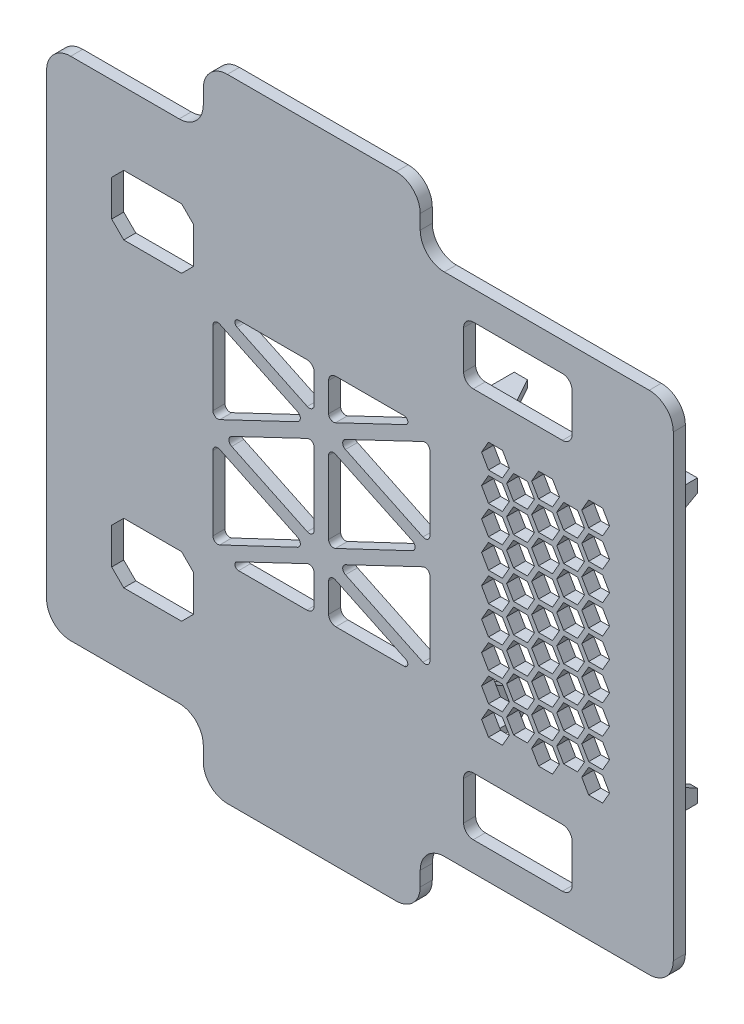
SolidWorks part; units mm, degrees
ref_plane "前视基准面" through (0, 0, 0) normal (0, 0, 1) x (1, 0, 0)
ref_plane "上视基准面" through (0, 0, 0) normal (0, 1, 0) x (1, 0, 0)
ref_plane "右视基准面" through (0, 0, 0) normal (1, 0, 0) x (0, 0, -1)
sketch "草图1" plane through (0, 0, 0) normal (0, 0, 1) x (1, 0, 0)
  line L2 (-130, 95) -> (-130, -95)
  line L3 (-120, -105) -> (-75, -105)
  line L4 (130, 95) -> (130, -95)
  line L5 (126.7518, 102.3765) -> (130, 105) construction
  line L6 (-130, -105) -> (-126.7518, -102.3765) construction
  line L9 (-65, -115) -> (-65, -121)
  line L10 (-55, -131) -> (15, -131)
  line L11 (25, -121) -> (25, -115)
  line L13 (35, -105) -> (120, -105)
  line L14 (126.7518, -102.3765) -> (130, -105) construction
  line L15 (-130, 105) -> (-126.7518, 102.3765) construction
  line L16 (-130, 0) -> (130, 0) construction
  line L17 (35, 105) -> (120, 105)
  line L18 (25, 121) -> (25, 115)
  line L19 (-55, 131) -> (15, 131)
  line L20 (-65, 115) -> (-65, 121)
  line L21 (-120, 105) -> (-75, 105)
  arc A1 (-120, -105) -> (-130, -95) centre (-120, -95) cw
  arc A3 (120, -105) -> (130, -95) centre (120, -95) ccw
  arc A8 (-65, -115) -> (-75, -105) centre (-75, -115) ccw
  arc A9 (25, -115) -> (35, -105) centre (35, -115) cw
  arc A10 (-55, -131) -> (-65, -121) centre (-55, -121) cw
  arc A11 (15, -131) -> (25, -121) centre (15, -121) ccw
  arc A12 (15, 131) -> (25, 121) centre (15, 121) cw
  arc A13 (-55, 131) -> (-65, 121) centre (-55, 121) ccw
  arc A14 (25, 115) -> (35, 105) centre (35, 115) ccw
  arc A15 (-65, 115) -> (-75, 105) centre (-75, 115) cw
  arc A16 (120, 105) -> (130, 95) centre (120, 95) cw
  arc A17 (-120, 105) -> (-130, 95) centre (-120, 95) ccw
  point P0 (0, 0)
  point P40 (25, -105)
  point P45 (25, 105)
  dimension "D2" = 10
  dimension "D3" = 65
  dimension "D4" = 10
  dimension "D5" = 105
  dimension "D7" = 10
  dimension "D8" = 10
  dimension "D10" = 10
  dimension "D12" = 10
  dimension "D13" = 105
  dimension "D18" = 90
  dimension "D19" = 6
extrude "凸台-拉伸1" add sketch "草图1" along normal blind 5
sketch "草图4" plane through (0, 0, 0) normal (0, 0, -1) x (-1, 0, 0)
  line L0 (-39, -47.5) -> (-39, -58.5)
  line L1 (-39, -58.5) -> (-50, -58.5)
  line L2 (-50, -58.5) -> (-50, -55.5)
  line L3 (-50, -55.5) -> (-42, -55.5)
  line L4 (-42, -55.5) -> (-42, -47.5)
  line L5 (-42, -47.5) -> (-39, -47.5)
  line L6 (-130, 0) -> (-25.5592, 0) construction
  line L7 (-130, -95) -> (-130, 95) construction
  line L10 (-130, -95) -> (-130, 95) construction
  dimension "D1" = 11
  dimension "D2" = 11
  dimension "D3" = 3
  dimension "D4" = 3
  dimension "D5" = 80
  dimension "D7" = 55.5
extrude "凸台-拉伸2" add sketch "草图4" along normal blind 20
sketch "草图5" plane through (0, -58.5, 0) normal (0, -1, 0) x (1, 0, 0)
  line L0 (50, -10) -> (44.5, -20)
  line L1 (50, -20) -> (50, 0) construction
  line L2 (50, -20) -> (39, -20) construction
  line L3 (44.5, -20) -> (50, -20)
  line L4 (50, -20) -> (50, -10)
  dimension "D1" = 10
  dimension "D2" = 5.5
extrude "切除-拉伸3" cut sketch "草图5" against normal blind 10
sketch "草图6" plane through (39, 0, 0) normal (-1, 0, 0) x (0, 0, 1)
  line L0 (-20, -53) -> (-10, -47.5)
  line L1 (-20, -58.5) -> (-20, -47.5) construction
  line L2 (-20, -47.5) -> (0, -47.5) construction
  line L3 (-10, -47.5) -> (-20, -47.5)
  line L4 (-20, -47.5) -> (-20, -53)
  dimension "D1" = 10
  dimension "D2" = 5.5
extrude "切除-拉伸4" cut sketch "草图6" against normal blind 10
ref_plane "基准面2" through (77, 0, 0) normal (1, 0, 0) x (0, 0, -1)
mirror "镜向1" about plane through (77, 0, 0) normal (1, 0, 0) of "凸台-拉伸2", "切除-拉伸4", "切除-拉伸3"
mirror "镜向2" about plane through (0, 0, 0) normal (0, 1, 0) of "镜向1"
sketch "草图7" plane through (0, 0, 0) normal (0, 0, -1) x (-1, 0, 0)
  line L4 (-112, -55.5) -> (-104, -55.5) construction
  line L5 (-112, 47.5) -> (-112, 55.5) construction
  line L6 (-112, 55.5) -> (-104, 55.5) construction
  line L7 (-92.013, 36) -> (-94.8997, 41)
  line L8 (-94.8997, 41) -> (-100.6732, 41)
  line L9 (-100.6732, 41) -> (-103.56, 36)
  line L10 (-103.56, 36) -> (-100.6732, 31)
  line L11 (-100.6732, 31) -> (-94.8997, 31)
  line L12 (-94.8997, 31) -> (-92.013, 36)
  line L13 (-77.0019, 36) -> (-97.7865, 36) construction
  line L14 (-74.1151, 31) -> (-71.2284, 36)
  line L15 (-71.2284, 36) -> (-74.1151, 41)
  line L16 (-74.1151, 41) -> (-79.8886, 41)
  line L17 (-79.8886, 41) -> (-82.7754, 36)
  line L18 (-82.7754, 36) -> (-79.8886, 31)
  line L19 (-79.8886, 31) -> (-74.1151, 31)
  line L20 (-92.013, 24) -> (-94.8997, 29)
  line L21 (-93.1677, 30) -> (-90.2809, 25)
  line L22 (-90.2809, 25) -> (-84.5074, 25)
  line L23 (-84.5074, 25) -> (-81.6207, 30)
  line L24 (-81.6207, 30) -> (-84.5074, 35)
  line L25 (-84.5074, 35) -> (-90.2809, 35)
  line L26 (-90.2809, 35) -> (-93.1677, 30)
  line L27 (-84.5074, 37) -> (-81.6207, 42)
  line L28 (-81.6207, 42) -> (-84.5074, 47)
  line L29 (-84.5074, 47) -> (-90.2809, 47)
  line L30 (-90.2809, 47) -> (-93.1677, 42)
  line L31 (-93.1677, 42) -> (-90.2809, 37)
  line L32 (-90.2809, 37) -> (-84.5074, 37)
  line L33 (-79.8886, 43) -> (-74.1151, 43)
  line L34 (-74.1151, 43) -> (-71.2284, 48)
  line L35 (-71.2284, 48) -> (-74.1151, 53)
  line L36 (-74.1151, 53) -> (-79.8886, 53)
  line L37 (-79.8886, 53) -> (-82.7754, 48)
  line L38 (-82.7754, 48) -> (-79.8886, 43)
  line L39 (-94.8997, 43) -> (-92.013, 48)
  line L40 (-92.013, 48) -> (-94.8997, 53)
  line L41 (-94.8997, 53) -> (-100.6732, 53)
  line L42 (-100.6732, 53) -> (-103.56, 48)
  line L43 (-103.56, 48) -> (-100.6732, 43)
  line L44 (-100.6732, 43) -> (-94.8997, 43)
  line L45 (-72.3831, 42) -> (-69.4963, 37)
  line L46 (-69.4963, 37) -> (-63.7228, 37)
  line L47 (-63.7228, 37) -> (-60.8361, 42)
  line L48 (-60.8361, 42) -> (-63.7228, 47)
  line L49 (-63.7228, 47) -> (-69.4963, 47)
  line L50 (-69.4963, 47) -> (-72.3831, 42)
  line L51 (-94.8997, 29) -> (-100.6732, 29)
  line L52 (-100.6732, 29) -> (-103.56, 24)
  line L53 (-103.56, 24) -> (-100.6732, 19)
  line L54 (-100.6732, 19) -> (-94.8997, 19)
  line L55 (-94.8997, 19) -> (-92.013, 24)
  line L56 (-93.1677, 18) -> (-90.2809, 13)
  line L57 (-90.2809, 13) -> (-84.5074, 13)
  line L58 (-84.5074, 13) -> (-81.6207, 18)
  line L59 (-81.6207, 18) -> (-84.5074, 23)
  line L60 (-84.5074, 23) -> (-90.2809, 23)
  line L61 (-90.2809, 23) -> (-93.1677, 18)
  line L62 (-74.1151, 19) -> (-71.2284, 24)
  line L63 (-71.2284, 24) -> (-74.1151, 29)
  line L64 (-74.1151, 29) -> (-79.8886, 29)
  line L65 (-79.8886, 29) -> (-82.7754, 24)
  line L66 (-82.7754, 24) -> (-79.8886, 19)
  line L67 (-79.8886, 19) -> (-74.1151, 19)
  line L68 (-72.3831, 30) -> (-69.4963, 25)
  line L69 (-69.4963, 25) -> (-63.7228, 25)
  line L70 (-63.7228, 25) -> (-60.8361, 30)
  line L71 (-60.8361, 30) -> (-63.7228, 35)
  line L72 (-63.7228, 35) -> (-69.4963, 35)
  line L73 (-69.4963, 35) -> (-72.3831, 30)
  line L74 (-92.013, 12) -> (-94.8997, 17)
  line L75 (-94.8997, 17) -> (-100.6732, 17)
  line L76 (-100.6732, 17) -> (-103.56, 12)
  line L77 (-103.56, 12) -> (-100.6732, 7)
  line L78 (-100.6732, 7) -> (-94.8997, 7)
  line L79 (-94.8997, 7) -> (-92.013, 12)
  line L80 (-93.1677, 6) -> (-90.2809, 1)
  line L81 (-90.2809, 1) -> (-84.5074, 1)
  line L82 (-84.5074, 1) -> (-81.6207, 6)
  line L83 (-81.6207, 6) -> (-84.5074, 11)
  line L84 (-84.5074, 11) -> (-90.2809, 11)
  line L85 (-90.2809, 11) -> (-93.1677, 6)
  line L86 (-74.1151, 7) -> (-71.2284, 12)
  line L87 (-71.2284, 12) -> (-74.1151, 17)
  line L88 (-74.1151, 17) -> (-79.8886, 17)
  line L89 (-79.8886, 17) -> (-82.7754, 12)
  line L90 (-82.7754, 12) -> (-79.8886, 7)
  line L91 (-79.8886, 7) -> (-74.1151, 7)
  line L92 (-72.3831, 18) -> (-69.4963, 13)
  line L93 (-69.4963, 13) -> (-63.7228, 13)
  line L94 (-63.7228, 13) -> (-60.8361, 18)
  line L95 (-60.8361, 18) -> (-63.7228, 23)
  line L96 (-63.7228, 23) -> (-69.4963, 23)
  line L97 (-69.4963, 23) -> (-72.3831, 18)
  line L98 (-92.013, 0) -> (-94.8997, 5)
  line L99 (-94.8997, 5) -> (-100.6732, 5)
  line L100 (-100.6732, 5) -> (-103.56, 0)
  line L101 (-103.56, 0) -> (-100.6732, -5)
  line L102 (-100.6732, -5) -> (-94.8997, -5)
  line L103 (-94.8997, -5) -> (-92.013, 0)
  line L104 (-93.1677, -6) -> (-90.2809, -11)
  line L105 (-90.2809, -11) -> (-84.5074, -11)
  line L106 (-84.5074, -11) -> (-81.6207, -6)
  line L107 (-81.6207, -6) -> (-84.5074, -1)
  line L108 (-84.5074, -1) -> (-90.2809, -1)
  line L109 (-90.2809, -1) -> (-93.1677, -6)
  line L110 (-74.1151, -5) -> (-71.2284, 0)
  line L111 (-71.2284, 0) -> (-74.1151, 5)
  line L112 (-74.1151, 5) -> (-79.8886, 5)
  line L113 (-79.8886, 5) -> (-82.7754, 0)
  line L114 (-82.7754, 0) -> (-79.8886, -5)
  line L115 (-79.8886, -5) -> (-74.1151, -5)
  line L116 (-72.3831, 6) -> (-69.4963, 1)
  line L117 (-69.4963, 1) -> (-63.7228, 1)
  line L118 (-63.7228, 1) -> (-60.8361, 6)
  line L119 (-60.8361, 6) -> (-63.7228, 11)
  line L120 (-63.7228, 11) -> (-69.4963, 11)
  line L121 (-69.4963, 11) -> (-72.3831, 6)
  line L122 (-92.013, -12) -> (-94.8997, -7)
  line L123 (-94.8997, -7) -> (-100.6732, -7)
  line L124 (-100.6732, -7) -> (-103.56, -12)
  line L125 (-103.56, -12) -> (-100.6732, -17)
  line L126 (-100.6732, -17) -> (-94.8997, -17)
  line L127 (-94.8997, -17) -> (-92.013, -12)
  line L128 (-93.1677, -18) -> (-90.2809, -23)
  line L129 (-90.2809, -23) -> (-84.5074, -23)
  line L130 (-84.5074, -23) -> (-81.6207, -18)
  line L131 (-81.6207, -18) -> (-84.5074, -13)
  line L132 (-84.5074, -13) -> (-90.2809, -13)
  line L133 (-90.2809, -13) -> (-93.1677, -18)
  line L134 (-74.1151, -17) -> (-71.2284, -12)
  line L135 (-71.2284, -12) -> (-74.1151, -7)
  line L136 (-74.1151, -7) -> (-79.8886, -7)
  line L137 (-79.8886, -7) -> (-82.7754, -12)
  line L138 (-82.7754, -12) -> (-79.8886, -17)
  line L139 (-79.8886, -17) -> (-74.1151, -17)
  line L140 (-72.3831, -6) -> (-69.4963, -11)
  line L141 (-69.4963, -11) -> (-63.7228, -11)
  line L142 (-63.7228, -11) -> (-60.8361, -6)
  line L143 (-60.8361, -6) -> (-63.7228, -1)
  line L144 (-63.7228, -1) -> (-69.4963, -1)
  line L145 (-69.4963, -1) -> (-72.3831, -6)
  line L146 (-92.013, -24) -> (-94.8997, -19)
  line L147 (-94.8997, -19) -> (-100.6732, -19)
  line L148 (-100.6732, -19) -> (-103.56, -24)
  line L149 (-103.56, -24) -> (-100.6732, -29)
  line L150 (-100.6732, -29) -> (-94.8997, -29)
  line L151 (-94.8997, -29) -> (-92.013, -24)
  line L152 (-93.1677, -30) -> (-90.2809, -35)
  line L153 (-90.2809, -35) -> (-84.5074, -35)
  line L154 (-84.5074, -35) -> (-81.6207, -30)
  line L155 (-81.6207, -30) -> (-84.5074, -25)
  line L156 (-84.5074, -25) -> (-90.2809, -25)
  line L157 (-90.2809, -25) -> (-93.1677, -30)
  line L158 (-74.1151, -29) -> (-71.2284, -24)
  line L159 (-71.2284, -24) -> (-74.1151, -19)
  line L160 (-74.1151, -19) -> (-79.8886, -19)
  line L161 (-79.8886, -19) -> (-82.7754, -24)
  line L162 (-82.7754, -24) -> (-79.8886, -29)
  line L163 (-79.8886, -29) -> (-74.1151, -29)
  line L164 (-72.3831, -18) -> (-69.4963, -23)
  line L165 (-69.4963, -23) -> (-63.7228, -23)
  line L166 (-63.7228, -23) -> (-60.8361, -18)
  line L167 (-60.8361, -18) -> (-63.7228, -13)
  line L168 (-63.7228, -13) -> (-69.4963, -13)
  line L169 (-69.4963, -13) -> (-72.3831, -18)
  line L170 (-92.013, -36) -> (-94.8997, -31)
  line L171 (-94.8997, -31) -> (-100.6732, -31)
  line L172 (-100.6732, -31) -> (-103.56, -36)
  line L173 (-103.56, -36) -> (-100.6732, -41)
  line L174 (-100.6732, -41) -> (-94.8997, -41)
  line L175 (-94.8997, -41) -> (-92.013, -36)
  line L176 (-93.1677, -42) -> (-90.2809, -47)
  line L177 (-90.2809, -47) -> (-84.5074, -47)
  line L178 (-84.5074, -47) -> (-81.6207, -42)
  line L179 (-81.6207, -42) -> (-84.5074, -37)
  line L180 (-84.5074, -37) -> (-90.2809, -37)
  line L181 (-90.2809, -37) -> (-93.1677, -42)
  line L182 (-74.1151, -41) -> (-71.2284, -36)
  line L183 (-71.2284, -36) -> (-74.1151, -31)
  line L184 (-74.1151, -31) -> (-79.8886, -31)
  line L185 (-79.8886, -31) -> (-82.7754, -36)
  line L186 (-82.7754, -36) -> (-79.8886, -41)
  line L187 (-79.8886, -41) -> (-74.1151, -41)
  line L188 (-72.3831, -30) -> (-69.4963, -35)
  line L189 (-69.4963, -35) -> (-63.7228, -35)
  line L190 (-63.7228, -35) -> (-60.8361, -30)
  line L191 (-60.8361, -30) -> (-63.7228, -25)
  line L192 (-63.7228, -25) -> (-69.4963, -25)
  line L193 (-69.4963, -25) -> (-72.3831, -30)
  line L194 (-92.013, -48) -> (-94.8997, -43)
  line L195 (-94.8997, -43) -> (-100.6732, -43)
  line L196 (-100.6732, -43) -> (-103.56, -48)
  line L197 (-103.56, -48) -> (-100.6732, -53)
  line L198 (-100.6732, -53) -> (-94.8997, -53)
  line L199 (-94.8997, -53) -> (-92.013, -48)
  line L206 (-74.1151, -53) -> (-71.2284, -48)
  line L207 (-71.2284, -48) -> (-74.1151, -43)
  line L208 (-74.1151, -43) -> (-79.8886, -43)
  line L209 (-79.8886, -43) -> (-82.7754, -48)
  line L210 (-82.7754, -48) -> (-79.8886, -53)
  line L211 (-79.8886, -53) -> (-74.1151, -53)
  line L212 (-72.3831, -42) -> (-69.4963, -47)
  line L213 (-69.4963, -47) -> (-63.7228, -47)
  line L214 (-63.7228, -47) -> (-60.8361, -42)
  line L215 (-60.8361, -42) -> (-63.7228, -37)
  line L216 (-63.7228, -37) -> (-69.4963, -37)
  line L217 (-69.4963, -37) -> (-72.3831, -42)
  line L218 (-61.9908, 36) -> (-59.104, 31)
  line L219 (-61.9908, 48) -> (-59.104, 43)
  line L220 (-59.104, 43) -> (-53.3305, 43)
  line L221 (-53.3305, 43) -> (-50.4438, 48)
  line L222 (-50.4438, 48) -> (-53.3305, 53)
  line L223 (-53.3305, 53) -> (-59.104, 53)
  line L224 (-59.104, 53) -> (-61.9908, 48)
  line L225 (-59.104, 31) -> (-53.3305, 31)
  line L226 (-53.3305, 31) -> (-50.4438, 36)
  line L227 (-50.4438, 36) -> (-53.3305, 41)
  line L228 (-53.3305, 41) -> (-59.104, 41)
  line L229 (-59.104, 41) -> (-61.9908, 36)
  line L230 (-61.9908, 24) -> (-59.104, 19)
  line L231 (-59.104, 19) -> (-53.3305, 19)
  line L232 (-53.3305, 19) -> (-50.4438, 24)
  line L233 (-50.4438, 24) -> (-53.3305, 29)
  line L234 (-53.3305, 29) -> (-59.104, 29)
  line L235 (-59.104, 29) -> (-61.9908, 24)
  line L236 (-61.9908, 12) -> (-59.104, 7)
  line L237 (-59.104, 7) -> (-53.3305, 7)
  line L238 (-53.3305, 7) -> (-50.4438, 12)
  line L239 (-50.4438, 12) -> (-53.3305, 17)
  line L240 (-53.3305, 17) -> (-59.104, 17)
  line L241 (-59.104, 17) -> (-61.9908, 12)
  line L242 (-61.9908, 0) -> (-59.104, -5)
  line L243 (-59.104, -5) -> (-53.3305, -5)
  line L244 (-53.3305, -5) -> (-50.4438, 0)
  line L245 (-50.4438, 0) -> (-53.3305, 5)
  line L246 (-53.3305, 5) -> (-59.104, 5)
  line L247 (-59.104, 5) -> (-61.9908, 0)
  line L248 (-61.9908, -12) -> (-59.104, -17)
  line L249 (-59.104, -17) -> (-53.3305, -17)
  line L250 (-53.3305, -17) -> (-50.4438, -12)
  line L251 (-50.4438, -12) -> (-53.3305, -7)
  line L252 (-53.3305, -7) -> (-59.104, -7)
  line L253 (-59.104, -7) -> (-61.9908, -12)
  line L254 (-61.9908, -24) -> (-59.104, -29)
  line L255 (-59.104, -29) -> (-53.3305, -29)
  line L256 (-53.3305, -29) -> (-50.4438, -24)
  line L257 (-50.4438, -24) -> (-53.3305, -19)
  line L258 (-53.3305, -19) -> (-59.104, -19)
  line L259 (-59.104, -19) -> (-61.9908, -24)
  line L260 (-61.9908, -36) -> (-59.104, -41)
  line L261 (-59.104, -41) -> (-53.3305, -41)
  line L262 (-53.3305, -41) -> (-50.4438, -36)
  line L263 (-50.4438, -36) -> (-53.3305, -31)
  line L264 (-53.3305, -31) -> (-59.104, -31)
  line L265 (-59.104, -31) -> (-61.9908, -36)
  line L266 (-61.9908, -48) -> (-59.104, -53)
  line L267 (-59.104, -53) -> (-53.3305, -53)
  line L268 (-53.3305, -53) -> (-50.4438, -48)
  line L269 (-50.4438, -48) -> (-53.3305, -43)
  line L270 (-53.3305, -43) -> (-59.104, -43)
  line L271 (-59.104, -43) -> (-61.9908, -48)
  line L272 (-93.1677, -54) -> (-90.2809, -59) [skipped]
  line L273 (-90.2809, -59) -> (-84.5074, -59) [skipped]
  line L274 (-84.5074, -59) -> (-81.6207, -54) [skipped]
  line L275 (-81.6207, -54) -> (-84.5074, -49) [skipped]
  line L276 (-84.5074, -49) -> (-90.2809, -49) [skipped]
  line L277 (-90.2809, -49) -> (-93.1677, -54) [skipped]
  circle A0 centre (-97.7865, 36) radius 5 construction
  circle A1 centre (-77.0019, 36) radius 5 construction
  circle A2 centre (-87.3942, 30) radius 5 construction
  circle A3 centre (-87.3942, 42) radius 5 construction
  circle A4 centre (-77.0019, 48) radius 5 construction
  circle A5 centre (-97.7865, 48) radius 5 construction
  circle A6 centre (-66.6096, 42) radius 5 construction
  circle A7 centre (-56.2173, 48) radius 5 construction
  point P4 (-87.3942, 37)
  dimension "D1" = 2
  dimension "D3" = 10
  dimension "D4" = 10
  dimension "D5" = 2
  dimension "D7" = 10
  dimension "D11" = 10
  dimension "D14" = 10
  dimension "D15" = 10
  dimension "D20" = 10
  dimension "D2" = 2
  dimension "D6" = 2
  dimension "D8" = 2
  dimension "D9" = 2
  dimension "D10" = 2
  dimension "D12" = 2
  dimension "D13" = 2
  dimension "D16" = 2
  dimension "D17" = 2
  dimension "D19" = 2
  dimension "D21" = 9
  dimension "D22" = 2.5
  dimension "D23" = 2.5
  dimension "D24" = 8.44
  dimension "D18" = 8
extrude "切除-拉伸5" cut sketch "草图7" against normal blind 5
sketch "草图8" plane through (0, 0, 0) normal (0, 0, -1) x (-1, 0, 0)
  line L0 (-75.3677, 120) -> (-75.3677, -120)
  line L1 (-100.0285, 77.2863) -> (-100.0285, -77.2863)
  line L2 (-100.0285, 77.2863) -> (-75.3677, 120)
  line L3 (-100.0285, -77.2863) -> (-75.3677, -120)
  line L4 (-37.1297, 0) -> (-146.8562, 0) construction
  dimension "D1" = 30
  dimension "D2" = 30
  dimension "D3" = 120
  dimension "D4" = 120
sketch "草图9" plane through (0, 0, 0) normal (0, 0, -1) x (-1, 0, 0)
  line L0 (148.8518, 0) -> (-37.1297, 0) construction
  line L1 (-29, 41) -> (-29, 4)
  line L2 (-25, -45) -> (13, -45)
  line L3 (61, -41) -> (61, -4)
  line L4 (57, 45) -> (19, 45)
  line L14 (-29, 41) -> (9.8049, 22.5)
  line L15 (57, 0) -> (19, -18.1163)
  line L16 (130, 95) -> (130, -95) construction
  line L17 (63, 93) -> (118, 93)
  line L18 (63, 93) -> (63, 66)
  line L19 (63, 66) -> (118, 66)
  line L20 (118, 93) -> (118, 66)
  line L21 (75, 105) -> (120, 105) construction
  line L22 (63, -66) -> (118, -66)
  line L23 (118, -93) -> (118, -66)
  line L24 (63, -93) -> (118, -93)
  line L25 (63, -93) -> (63, -66)
  line L26 (-120, 105) -> (-35, 105) construction
  line L27 (-43, 93) -> (-88, 93)
  line L28 (-43, 93) -> (-43, 69)
  line L29 (-43, 69) -> (-88, 69)
  line L30 (-88, 93) -> (-88, 69)
  line L31 (-130, -95) -> (-130, 95) construction
  line L32 (-43, -69) -> (-88, -69)
  line L33 (-88, -93) -> (-88, -69)
  line L34 (-43, -93) -> (-88, -93)
  line L35 (-43, -93) -> (-43, -69)
  line L36 (-25, 45) -> (13, 26.8837)
  line L37 (-25, -45) -> (13, -26.8837)
  line L38 (61, 41) -> (22.0746, 22.5575)
  line L39 (-25.5359, 0) -> (13, -18.258)
  line L40 (57, 45) -> (19, 26.8837)
  line L41 (57, -45) -> (19, -26.8837)
  line L42 (16, 61.4977) -> (16, -60.5731) construction
  line L43 (13, 45) -> (13, 26.8837)
  line L44 (19, 45) -> (19, 26.8837)
  line L45 (13, 18.258) -> (13, -18.258)
  line L46 (9.8049, 22.5) -> (-29, 4)
  line L47 (19, 18.1163) -> (57, 0)
  line L48 (22.0746, 22.5575) -> (61, 4)
  line L49 (13, 18.258) -> (-25.5359, 0)
  line L50 (19, 18.1163) -> (19, -18.1163)
  line L51 (22.0746, -22.5575) -> (61, -41)
  line L52 (9.8049, -22.5) -> (-29, -41)
  line L53 (9.8049, -22.5) -> (-29, -4)
  line L54 (22.0746, -22.5575) -> (61, -4)
  line L55 (13, -26.8837) -> (13, -45)
  line L56 (19, -26.8837) -> (19, -45)
  line L57 (13, 45) -> (-25, 45)
  line L58 (-29, -4) -> (-29, -41)
  line L59 (19, -45) -> (57, -45)
  line L60 (61, 4) -> (61, 41)
  line L61 (-44, 41) -> (-44, -37.8122) construction
  dimension "D1" = 45
  dimension "D2" = 45
  dimension "D3" = 15
  dimension "D4" = 90
  dimension "D5" = 1
  dimension "D7" = 12
  dimension "D8" = 12
  dimension "D9" = 27
  dimension "D10" = 55
  dimension "D11" = 12
  dimension "D12" = 45
  dimension "D13" = 42
  dimension "D14" = 24
  dimension "D21" = 4
  dimension "D22" = 4
  dimension "D23" = 4
  dimension "D24" = 4
  dimension "D26" = 4
  dimension "D27" = 3
  dimension "D28" = 45
extrude "切除-拉伸6" cut sketch "草图9" against normal blind 5 contours L27 L30 L29 L28 | L34 L35 L32 L33 | L4 L44 L40 | L48 L60 L38 | L47 L50 L15 | L54 L51 L3 | L56 L59 L41 | L55 L37 L2 | L53 L58 L52 | L45 L49 L39 | L46 L14 L1 | L43 L57 L36 | L57 L36 L43 region at (16.065, 22.5, 0) region at (-0.3333, -38.9612, 0) region at (-48.0249, -22.5192, 0) region at (-31.6667, 38.9612, 0) region at (-31.6667, 0, 0) region at (65.5, 81, 0) region at (65.5, -81, 0) region at (-0.3333, 38.9612, 0) region at (-48.0249, 22.5192, 0) region at (-0.1547, 0, 0) region at (-31.6667, -38.9612, 0) region at (16.065, -22.5, 0)
fillet "圆角1" radius 4 8 edges at (43, -93, 2.5) (88, -69, 2.5) (43, -69, 2.5) (88, -93, 2.5) (88, 69, 2.5) (43, 69, 2.5) (43, 93, 2.5) (88, 93, 2.5)
fillet "圆角2" radius 1.5 4 edges at (25, -45, 2.5) (-57, -45, 2.5) (25, 45, 2.5) (-57, 45, 2.5)
fillet "圆角3" radius 2 22 edges at (29, -4, 2.5) (29, 4, 2.5) (-13, -18.258, 2.5) (-61, -41, 2.5) (-61, 4, 2.5) (-13, -26.8837, 2.5) (-13, 18.258, 2.5) (-61, -4, 2.5) (-22.0746, -22.5575, 2.5) (25.5359, 0, 2.5) (-22.0746, 22.5575, 2.5) (-61, 41, 2.5) (-19, 26.8837, 2.5) (-19, -26.8837, 2.5) (-19, -18.1163, 2.5) (29, -41, 2.5) (29, 41, 2.5) (-57, 0, 2.5) (-9.8049, -22.5, 2.5) (-13, 26.8837, 2.5) (-9.8049, 22.5, 2.5) (-19, 18.1163, 2.5)
fillet "圆角4" radius 3 4 edges at (-13, -45, 2.5) (-13, 45, 2.5) (-19, -45, 2.5) (-19, 45, 2.5)
sketch "草图10" plane through (0, 0, 0) normal (0, 0, -1) x (-1, 0, 0)
  line L0 (-37.1297, 0) -> (-146.8562, 0) construction
  line L1 (-37.1297, 0) -> (-146.8562, 0) construction
  circle A0 centre (-119.4219, 72.4542) radius 1.8 construction
  circle A1 centre (-109.0164, 65.5279) radius 1.8 construction
  circle A2 centre (-104.184, 95.3465) radius 1.8 construction
  circle A3 centre (-93.7785, 88.4202) radius 1.8 construction
  circle A4 centre (-3.75, 104) radius 2.15 construction
  circle A5 centre (-3.75, 104) radius 2.15
  circle A6 centre (-3.75, -104) radius 2.15
  circle A11 centre (-13.0267, 121.679) radius 2.5 construction
  circle A12 centre (56.0941, 121.679) radius 2.45 construction
  circle A13 centre (30.0941, 121.679) radius 2.5 construction
  circle A14 centre (12.9733, 121.679) radius 2.45 construction
  circle A15 centre (-119.4219, 72.4542) radius 1.8
  circle A16 centre (-109.0164, 65.5279) radius 1.8
  circle A17 centre (-104.184, 95.3465) radius 1.8
  circle A18 centre (-93.7785, 88.4202) radius 1.8
  circle A26 centre (-13.0267, 121.679) radius 2.5
  circle A27 centre (56.0941, 121.679) radius 2.45
  circle A28 centre (30.0941, 121.679) radius 2.5
  circle A29 centre (12.9733, 121.679) radius 2.45
  circle A30 centre (12.9733, -121.679) radius 2.45
  circle A31 centre (30.0941, -121.679) radius 2.5
  circle A32 centre (56.0941, -121.679) radius 2.45
  circle A33 centre (-13.0267, -121.679) radius 2.5
  circle A41 centre (-93.7785, -88.4202) radius 1.8
  circle A42 centre (-104.184, -95.3465) radius 1.8
  circle A43 centre (-109.0164, -65.5279) radius 1.8
  circle A44 centre (-119.4219, -72.4542) radius 1.8
  circle A45 centre (-99.5, 59.5) radius 1.5 construction
  circle A46 centre (-84.5, 59.5) radius 1.5 construction
  circle A47 centre (-69.5, 59.5) radius 1.5 construction
  circle A48 centre (-54.5, 59.5) radius 1.5 construction
  circle A49 centre (0.8061, 58.25) radius 1.5 construction
  circle A50 centre (6.8061, 58.25) radius 1.5 construction
  circle A51 centre (24.8061, 58.25) radius 1.5 construction
  circle A52 centre (30.8061, 58.25) radius 1.5 construction
  circle A53 centre (-99.5, 59.5) radius 1.5
  circle A54 centre (-84.5, 59.5) radius 1.5
  circle A55 centre (-69.5, 59.5) radius 1.5
  circle A56 centre (-54.5, 59.5) radius 1.5
  circle A57 centre (0.8061, 58.25) radius 1.5
  circle A58 centre (6.8061, 58.25) radius 1.5
  circle A59 centre (24.8061, 58.25) radius 1.5
  circle A60 centre (30.8061, 58.25) radius 1.5
  circle A61 centre (30.8061, -58.25) radius 1.5
  circle A62 centre (24.8061, -58.25) radius 1.5
  circle A63 centre (6.8061, -58.25) radius 1.5
  circle A64 centre (0.8061, -58.25) radius 1.5
  circle A65 centre (-54.5, -59.5) radius 1.5
  circle A66 centre (-69.5, -59.5) radius 1.5
  circle A67 centre (-84.5, -59.5) radius 1.5
  circle A68 centre (-99.5, -59.5) radius 1.5
  circle A89 centre (75.897, 30.3) radius 1.5 construction
  circle A90 centre (85.897, 30.3) radius 1.5 construction
  circle A91 centre (75.897, 30.3) radius 1.5
  circle A92 centre (85.897, 30.3) radius 1.5
  circle A93 centre (85.897, -30.3) radius 1.5
  circle A94 centre (75.897, -30.3) radius 1.5
  circle A95 centre (43.75, 83) radius 2.15 construction
  circle A96 centre (43.75, 104) radius 2.15 construction
  circle A97 centre (-3.75, 83) radius 2.15 construction
  circle A99 centre (43.75, 83) radius 2.15
  circle A100 centre (43.75, 104) radius 2.15
  circle A101 centre (-3.75, 83) radius 2.15
  circle A104 centre (-3.75, -83) radius 2.15
  circle A105 centre (43.75, -104) radius 2.15
  circle A106 centre (43.75, -83) radius 2.15
extrude "切除-拉伸7" [suppressed] cut sketch "草图10" against normal through all
sketch "草图11" plane through (0, 0, 0) normal (0, 0, -1) x (-1, 0, 0)
  line L0 (130, 95) -> (130, -95) construction
  line L1 (74, -75) -> (98, -75)
  line L2 (69, -70) -> (69, -55)
  line L3 (74, -50) -> (98, -50)
  line L4 (103, -70) -> (103, -55)
  line L5 (130, 0) -> (108.529, 0) construction
  line L10 (69, -70) -> (74, -75)
  line L11 (69, -55) -> (74, -50)
  line L12 (98, -50) -> (103, -55)
  line L13 (98, -75) -> (103, -70)
  line L14 (98, 75) -> (103, 70)
  line L15 (98, 50) -> (103, 55)
  line L16 (69, 55) -> (74, 50)
  line L17 (69, 70) -> (74, 75)
  line L18 (103, 70) -> (103, 55)
  line L19 (74, 50) -> (98, 50)
  line L20 (69, 70) -> (69, 55)
  line L21 (74, 75) -> (98, 75)
  point P0 (69, -75)
  point P1 (103, -50)
  point P2 (69, -50)
  point P3 (103, -75)
  point P8 (103, 75)
  point P9 (69, 50)
  point P10 (103, 50)
  point P11 (69, 75)
  dimension "D1" = 34
  dimension "D2" = 25
  dimension "D3" = 27
  dimension "D4" = 50
extrude "切除-拉伸8" cut sketch "草图11" against normal through all
equation "\"45、\"=43.7672"
